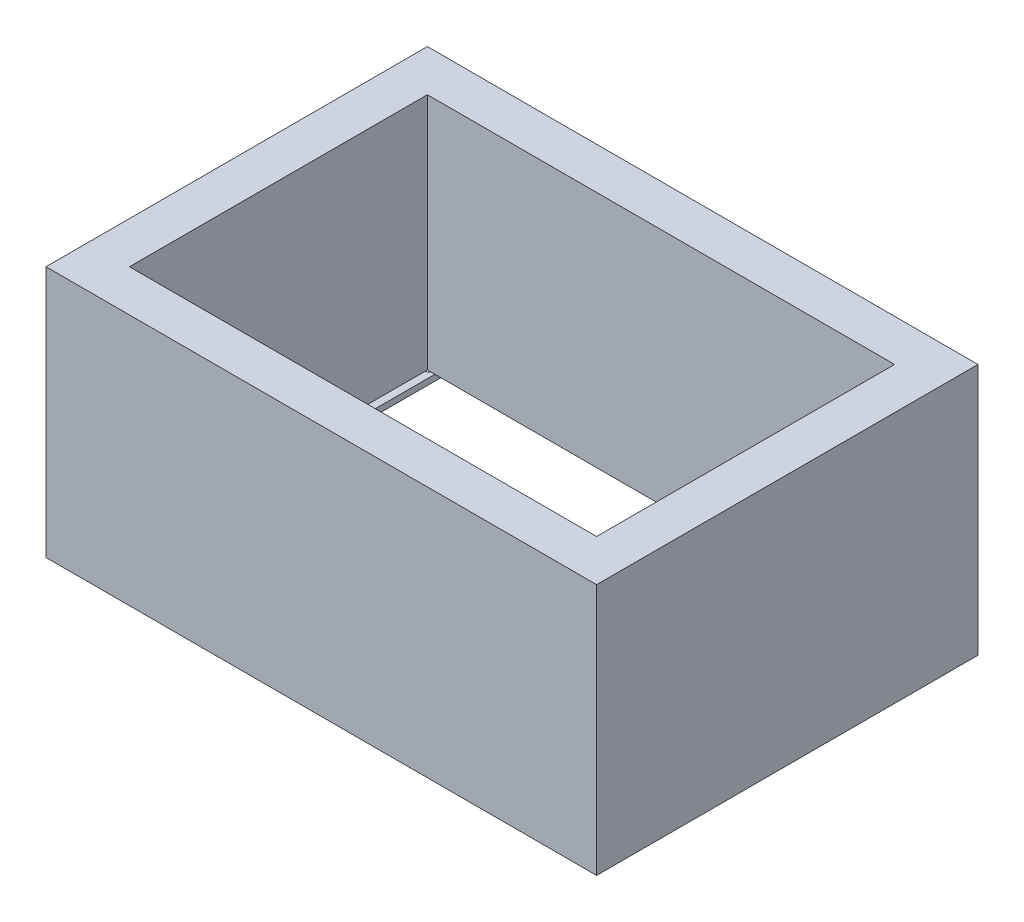
SolidWorks part; units mm, degrees
ref_plane "Front Plane" through (0, 0, 0) normal (0, 0, 1) x (1, 0, 0)
ref_plane "Top Plane" through (0, 0, 0) normal (0, 1, 0) x (1, 0, 0)
ref_plane "Right Plane" through (0, 0, 0) normal (1, 0, 0) x (0, 0, -1)
sketch "Sketch1" plane through (0, 0, 0) normal (0, 1, 0) x (1, 0, 0)
  line L0 (0, -99.7309) -> (0, 93.4243) construction
  line L1 (-56.134, -38.1) -> (56.134, -38.1)
  line L2 (-56.134, -38.1) -> (-56.134, 38.1)
  line L3 (-56.134, 38.1) -> (56.134, 38.1)
  line L4 (56.134, -38.1) -> (56.134, 38.1)
  line L5 (-56.134, -38.1) -> (56.134, 38.1) construction
  line L6 (-56.134, 38.1) -> (56.134, -38.1) construction
  line L7 (-35.56, -26.67) -> (35.56, -26.67) construction
  line L8 (-35.56, -26.67) -> (-35.56, 26.67) construction
  line L9 (-35.56, 26.67) -> (35.56, 26.67) construction
  line L10 (35.56, -26.67) -> (35.56, 26.67) construction
  line L11 (-35.56, -26.67) -> (35.56, 26.67) construction
  line L12 (-35.56, 26.67) -> (35.56, -26.67) construction
  line L13 (-133.3661, 0) -> (145.6083, -0.8038) construction
  line L14 (-58.674, -40.64) -> (-58.674, 40.64)
  line L15 (-58.674, 40.64) -> (58.674, 40.64)
  line L16 (58.674, -40.64) -> (58.674, 40.64)
  line L17 (-58.674, -40.64) -> (58.674, -40.64)
  line L18 (-49.784, -31.75) -> (-49.784, 31.75)
  line L19 (-49.784, 31.75) -> (49.784, 31.75)
  line L20 (49.784, -31.75) -> (49.784, 31.75)
  line L21 (-49.784, -31.75) -> (49.784, -31.75)
  line L22 (-56.134, 38.1) -> (-56.134, 40.64)
  line L23 (56.134, 38.1) -> (56.134, 40.64)
  circle A0 centre (-51.816, 34.29) radius 1.524
  circle A1 centre (52.324, 34.29) radius 1.524
  circle A3 centre (52.324, -34.29) radius 1.524
  circle A4 centre (-51.816, -34.29) radius 1.524
  point P0 (0, 0)
  point P6 (0, 0)
  dimension "D7" = 3.048
  dimension "D1" = 76.2
  dimension "D2" = 112.268
  dimension "D3" = 71.12
  dimension "D4" = 53.34
  dimension "D5" = 3.81
  dimension "D6" = 4.318
  dimension "D10" = 3.81
  dimension "D11" = 3.81
  dimension "D8" = 2.54
  dimension "D9" = 6.35
extrude "Boss-Extrude1" add sketch "Sketch1" along normal blind 50.8 contours L14 L17 L16 L15 L4 L1 L2 L3 | A1 | A3 | A1 | A0 | A4 | L14 L15 L16 L17 | L18 L19 L20 L21 region at (-54.7771, 0, 0) region at (0, 0, 39.5275) region at (-51.816, 0, -34.29) region at (52.324, 0, -34.29) region at (52.324, 0, 34.29) region at (-51.816, 0, 34.29)
extrude "Boss-Extrude2" add sketch "Sketch1<6>" against normal blind 1.6 contours L14 L17 L16 L15 L4 L1 L2 L3 region at (0, 0, 39.5275)
sketch "Sketch1<6>" plane through (0, 0, 0) normal (0, 1, 0) x (1, 0, 0) same geometry as "Sketch1"
sketch "Sketch2" plane through (0, -1.6, 0) normal (0, -1, 0) x (1, 0, 0)
  line L0 (58.674, 40.64) -> (58.674, -40.64) construction
  line L1 (-58.674, 40.64) -> (58.674, 40.64)
  line L2 (-58.674, 40.64) -> (-58.674, 34.29)
  line L3 (-58.674, 34.29) -> (58.674, 34.29)
  line L4 (58.674, 40.64) -> (58.674, 34.29)
  line L5 (-49.784, 31.75) -> (-49.784, -31.75) construction
  line L7 (-58.674, -40.64) -> (-49.784, -40.64)
  line L8 (-58.674, -40.64) -> (-58.674, 34.29)
  line L9 (-58.674, 34.29) -> (-49.784, 34.29)
  line L10 (-49.784, -40.64) -> (-49.784, 34.29)
  line L11 (-56.134, -40.64) -> (56.134, -40.64) construction
  line L12 (58.674, 34.29) -> (49.784, 34.29)
  line L13 (58.674, 34.29) -> (58.674, -40.64)
  line L14 (58.674, -40.64) -> (49.784, -40.64)
  line L15 (49.784, 34.29) -> (49.784, -40.64)
  line L16 (49.784, 31.75) -> (49.784, -31.75) construction
  line L18 (-49.784, -31.75) -> (49.784, -31.75)
  line L19 (-49.784, -31.75) -> (-49.784, -40.64)
  line L20 (-49.784, -40.64) -> (49.784, -40.64)
  line L21 (49.784, -31.75) -> (49.784, -40.64)
  line M5 (56.134, 38.1) -> (56.134, -40.64)
  line M6 (56.134, -40.64) -> (58.674, -40.64)
  line M7 (58.674, -40.64) -> (58.674, 40.64)
  line M8 (58.674, 40.64) -> (-58.674, 40.64)
  line M9 (-58.674, 40.64) -> (-58.674, -40.64)
  line M10 (-58.674, -40.64) -> (-56.134, -40.64)
  line M11 (-56.134, -40.64) -> (-56.134, 38.1)
  line M12 (-56.134, 38.1) -> (56.134, 38.1)
  dimension "D1" = 6.35
extrude "Boss-Extrude3" add sketch "Sketch2" along normal blind 1.27 contours L3 M9 M10 M11 | L7 L10 L3 M11 | L3 L15 L14 M5 | L3 M5 M6 M7 | L3 M11 M5 M12 | L3 M9 M11 M12 M5 M7 M8 region at (0, -1.6, 39.1764) region at (-57.404, -1.6, -3.175) region at (57.404, -1.6, -3.175) region at (0, -1.6, 36.195) region at (-52.959, -1.6, -3.175) region at (52.959, -1.6, -3.175)
extrude "Cut-Extrude1" cut sketch "Sketch1<5>" along normal blind 12.7 and the other way through all contours A0 | A4 | A3 | A1
sketch "Sketch1<5>" plane through (0, 0, 0) normal (0, 1, 0) x (1, 0, 0) same geometry as "Sketch1"
equation "\"PCB_Width\" = 4.42in"
equation "\"D2@Sketch1\"=\"PCB_Width\""
equation "\"PCB_Height\" = 3in"
equation "\"D1@Sketch1\"=\"PCB_Height\""
equation "\"PCB_Hole_Diameter\" = 0.12in"
equation "\"Sensor_Width\"= 0.07in * 40"
equation "\"Sensor_Height\"= 0.07in * 30"
equation "\"D3@Sketch1\"=\"Sensor_Width\""
equation "\"D4@Sketch1\"=\"Sensor_Height\""
equation "\"Hole_Horizontal_Offset\"= 0.17in"
equation "\"Hole_Vertical_Offset\"= 0.15in"
equation "\"PCB_Thickness\"= 1.6mm"
equation "\"D7@Sketch1\"=\"PCB_Hole_Diameter\""
equation "\"D1@Boss-Extrude2\"=\"PCB_Thickness\""
equation "\"D5@Sketch1\"=\"Hole_Vertical_Offset\""
equation "\"D10@Sketch1\"=\"Hole_Vertical_Offset\""
equation "\"D6@Sketch1\"=\"Hole_Horizontal_Offset\""
